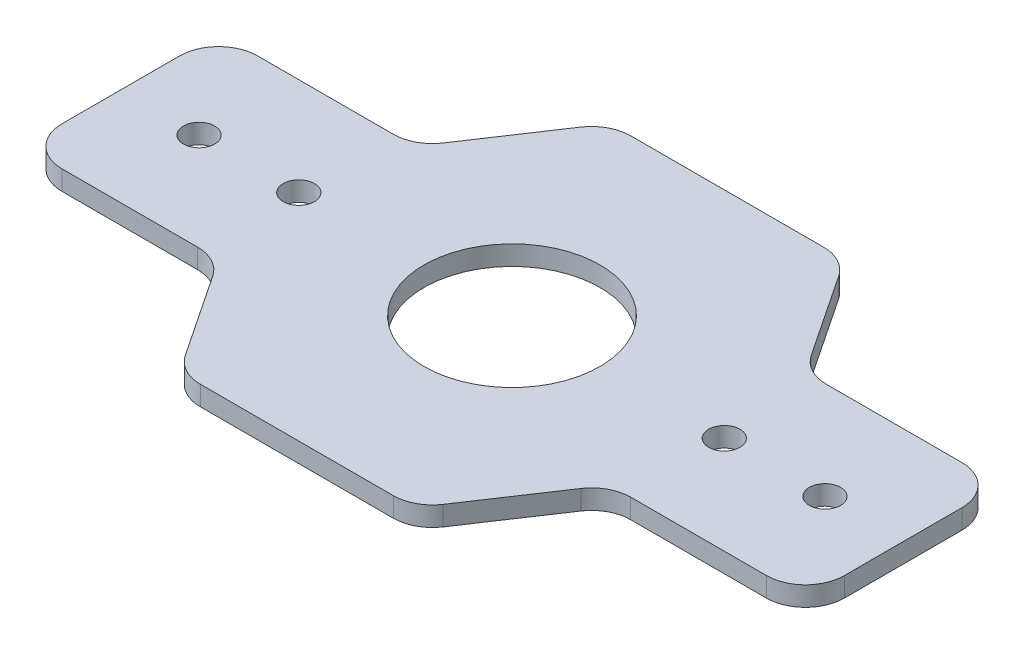
SolidWorks part; units mm, degrees
ref_plane "Front Plane" through (0, 0, 0) normal (0, 0, 1) x (1, 0, 0)
ref_plane "Top Plane" through (0, 0, 0) normal (0, 1, 0) x (1, 0, 0)
ref_plane "Right Plane" through (0, 0, 0) normal (1, 0, 0) x (0, 0, -1)
sketch "Sketch1" plane through (0, 0, 0) normal (0, 1, 0) x (1, 0, 0)
  line L0 (16.2686, 0) -> (85.3314, 0) construction
  line L1 (50.8, 0) -> (50.8, 3.1391) construction
  line L2 (19.05, 15.875) -> (31.75, 34.925)
  line L3 (-12.7, 15.875) -> (19.05, 15.875)
  line L4 (-12.7, 15.875) -> (-12.7, -15.875)
  line L5 (-12.7, -15.875) -> (19.05, -15.875)
  line L6 (114.3, 15.875) -> (114.3, -15.875)
  line L7 (-12.7, 15.875) -> (114.3, -15.875) construction
  line L8 (-12.7, -15.875) -> (114.3, 15.875) construction
  line L9 (31.75, 34.925) -> (69.85, 34.925)
  line L10 (69.85, 34.925) -> (82.55, 15.875)
  line L11 (50.8, 34.925) -> (50.8, 29.0511) construction
  line L12 (69.85, -34.925) -> (82.55, -15.875)
  line L13 (31.75, -34.925) -> (69.85, -34.925)
  line L14 (19.05, -15.875) -> (31.75, -34.925)
  line L15 (82.55, -15.875) -> (114.3, -15.875)
  line L16 (82.55, 15.875) -> (114.3, 15.875)
  circle A0 centre (0, 0) radius 2.54
  circle A1 centre (101.6, 0) radius 2.54
  circle A2 centre (16.2686, 0) radius 2.54 construction
  circle A3 centre (85.3314, 0) radius 2.54 construction
  point P13 (0, 0)
  point P22 (50.8, 29.0511)
  point P23 (70.6564, 33.2441)
  point P24 (85.3314, 15.875)
  point P25 (72.8128, 34.925)
  dimension "D1" = 5.08
  dimension "D3" = 127
  dimension "D4" = 31.75
  dimension "D5" = 69.0628
  dimension "D2" = 101.6
  dimension "D6" = 19.05
  dimension "D7" = 31.75
  dimension "D8" = 38.1
extrude "Boss-Extrude1" add sketch "Sketch1" along normal blind 3.175
fillet "Fillet1" radius 6.35 12 edges at (19.05, 1.5875, -15.875) (31.75, 1.5875, -34.925) (69.85, 1.5875, -34.925) (82.55, 1.5875, -15.875) (114.3, 1.5875, -15.875) (114.3, 1.5875, 15.875) (82.55, 1.5875, 15.875) (69.85, 1.5875, 34.925) (31.75, 1.5875, 34.925) (19.05, 1.5875, 15.875) (-12.7, 1.5875, -15.875) (-12.7, 1.5875, 15.875)
sketch "Sketch2" plane through (0, 3.175, 0) normal (0, 1, 0) x (1, 0, 0)
  circle A0 centre (50.8, 0) radius 14.2875
  circle A1 centre (0, 0) radius 2.54 construction
  dimension "D1" = 50.8
  dimension "D2" = 28.575
extrude "Cut-Extrude1" cut sketch "Sketch2" against normal blind 3.175
sketch "Sketch3" plane through (0, 3.175, 0) normal (0, 1, 0) x (1, 0, 0)
  circle A2 centre (85.2557, 0) radius 2.54
  circle A3 centre (16.1929, 0) radius 2.54
  circle A4 centre (101.6, 0) radius 2.54 construction
  point P6 (85.3314, 3.6706)
  dimension "D1" = 69.0628
  dimension "D2" = 5.08
  dimension "D3" = 5.08
  dimension "D4" = 16.3443
extrude "Cut-Extrude2" cut sketch "Sketch3" against normal through all
